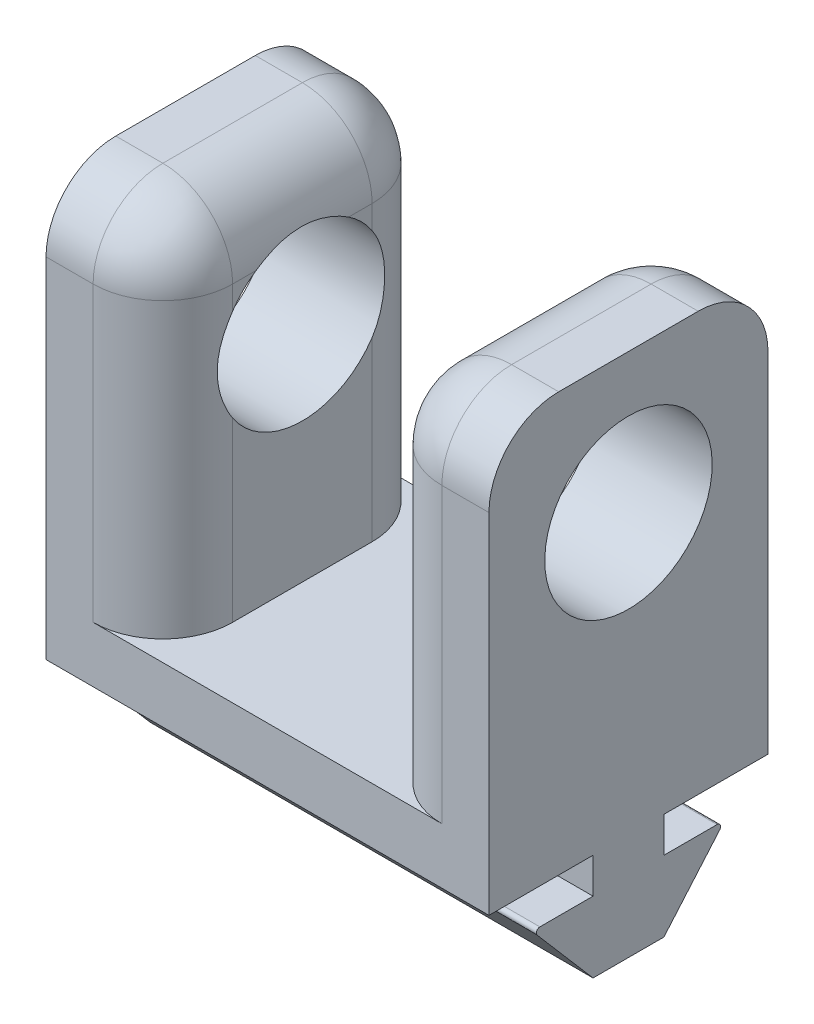
SolidWorks part; units mm, degrees
ref_plane "Front Plane" through (0, 0, 0) normal (0, 0, 1) x (1, 0, 0)
ref_plane "Top Plane" through (0, 0, 0) normal (0, 1, 0) x (1, 0, 0)
ref_plane "Right Plane" through (0, 0, 0) normal (1, 0, 0) x (0, 0, -1)
sketch "Sketch1" plane through (0, 0, 0) normal (0, 1, 0) x (1, 0, 0)
  line L1 (38.1, -25.4) -> (-38.1, -25.4)
  line L2 (38.1, -25.4) -> (38.1, 25.4)
  line L3 (38.1, 25.4) -> (-38.1, 25.4)
  line L4 (-38.1, -25.4) -> (-38.1, 25.4)
  line L5 (38.1, -25.4) -> (-38.1, 25.4) construction
  line L6 (38.1, 25.4) -> (-38.1, -25.4) construction
  point P0 (0, 0)
  dimension "D1" = 76.2
  dimension "D2" = 50.8
sketch "Sketch10" plane through (0, 0, 0) normal (1, 0, 0) x (0, 0, -1)
  line L0 (-12.7, 0) -> (0, 0) construction
  line L1 (0, 0) -> (0, -12.7) construction
  line L2 (0, 0) -> (0, 12.7) construction
  line L3 (0, 0) -> (12.7, 0) construction
  line L4 (6.35, 10.16) -> (-6.35, 10.16)
  line L5 (-6.5427, 9.7405) -> (-2.54, 5.08)
  line L6 (6.5427, 9.7405) -> (2.54, 5.08)
  line L7 (2.54, 5.08) -> (-2.54, 5.08)
  line L8 (-5.08, -2.54) -> (-5.08, 2.54)
  line L9 (-5.08, 2.54) -> (-9.7405, 6.5427)
  line L10 (-10.16, -6.35) -> (-10.16, 6.35)
  line L11 (-9.7405, -6.5427) -> (-5.08, -2.54)
  line L12 (-12.7, -2.54) -> (-12.7, 2.54)
  line L13 (-12.7, 2.54) -> (-10.16, 2.54)
  line L14 (-10.16, 2.54) -> (-10.16, -2.54)
  line L15 (-10.16, -2.54) -> (-12.7, -2.54)
  line L16 (2.54, 12.7) -> (-2.54, 12.7)
  line L17 (-2.54, 12.7) -> (-2.54, 10.16)
  line L18 (-2.54, 10.16) -> (2.54, 10.16)
  line L19 (2.54, 10.16) -> (2.54, 12.7)
  line L20 (2.54, -12.7) -> (-2.54, -12.7)
  line L21 (2.54, -5.08) -> (-2.54, -5.08)
  line L23 (6.35, -10.16) -> (-6.35, -10.16)
  line L24 (-2.54, -12.7) -> (-2.54, -10.16)
  line L26 (2.54, -12.7) -> (2.54, -10.16)
  line L27 (-2.54, -10.16) -> (2.54, -10.16)
  line L28 (-2.54, -5.08) -> (-6.5427, -9.7405)
  line L29 (2.54, -5.08) -> (6.5427, -9.7405)
  line L30 (5.08, -2.54) -> (5.08, 2.54)
  line L31 (12.7, -2.54) -> (12.7, 2.54)
  line L32 (12.7, 2.54) -> (10.16, 2.54)
  line L33 (10.16, 2.54) -> (10.16, -2.54)
  line L34 (10.16, -2.54) -> (12.7, -2.54)
  line L35 (10.16, -6.35) -> (10.16, 6.35)
  line L36 (5.08, 2.54) -> (9.7405, 6.5427)
  line L37 (5.08, -2.54) -> (9.7405, -6.5427)
  arc A0 (-10.16, -6.35) -> (-9.7405, -6.5427) centre (-9.906, -6.35) ccw
  arc A1 (-9.7405, 6.5427) -> (-10.16, 6.35) centre (-9.906, 6.35) ccw
  arc A2 (6.35, 10.16) -> (6.5427, 9.7405) centre (6.35, 9.906) cw
  arc A3 (-6.35, 10.16) -> (-6.5427, 9.7405) centre (-6.35, 9.906) ccw
  arc A4 (-6.35, -10.16) -> (-6.5427, -9.7405) centre (-6.35, -9.906) cw
  arc A6 (6.5427, -9.7405) -> (6.35, -10.16) centre (6.35, -9.906) cw
  arc A8 (9.7405, -6.5427) -> (10.16, -6.35) centre (9.906, -6.35) ccw
  arc A9 (10.16, 6.35) -> (9.7405, 6.5427) centre (9.906, 6.35) ccw
  point P4 (0, 5.08)
  point P10 (0, 10.16)
  point P17 (-5.08, 0)
  point P20 (-10.16, 0)
  point P30 (-12.7, 0)
  point P35 (0, 12.7)
  point P39 (0, -12.7)
  point P42 (0, -5.08)
  point P46 (0, -10.16)
  point P52 (5.08, 0)
  point P55 (12.7, 0)
  point P60 (10.16, 0)
  dimension "D1" = 0.254
  dimension "D16" = 0.254
  dimension "D2" = 5.08
  dimension "D3" = 5.08
  dimension "D4" = 2.54
  dimension "D5" = 2.54
  dimension "D6" = 5.08
  dimension "D7" = 12.7
  dimension "D8" = 5.08
  dimension "D9" = 12.7
  dimension "D10" = 5.08
  dimension "D11" = 5.08
  dimension "D12" = 12.7
  dimension "D13" = 5.08
  dimension "D14" = 5.08
  dimension "D15" = 2.54
extrude "Boss-Extrude3" add sketch "Sketch10" against normal blind 31.75 separate body contours L15 L10 L13 | L9 A1 L10 A0 L11 L8 | L4 A3 L5 L7 L6 A2 | L4 L19 L17 | A6 L29 L21 L28 A4 L23 | L20 L26 L23 L24 | L35 A9 L36 L30 L37 A8 L33 | L33 L34 L31 L32 region at (0, 8.0055, 0) region at (0, 11.43, 0) region at (0, 0, 8.0055) region at (0, 0, 11.43) region at (0, -11.43, 0) region at (0, -8.0055, 0) region at (0, 0, -8.0055) region at (0, 0, -11.43)
sketch "Sketch11" plane through (0, 0, 0) normal (1, 0, 0) x (0, 0, -1)
  line L0 (10, 12.7) -> (-10, 12.7)
  line L2 (-10, 12.7) -> (-10, 16.7)
  line L3 (-10, 16.7) -> (10, 16.7)
  line L4 (10, 16.7) -> (10, 12.7)
  line L5 (2.54, 12.7) -> (-2.54, 12.7) construction
  point P3 (0, 12.7)
  dimension "D1" = 4
  dimension "D2" = 20
extrude "Boss-Extrude4" add sketch "Sketch11" along direction (1, 0, 0) on the side against the normal up to surface (31.75 mm away) up to face at (-31.75, 9.5805, 0)
sketch "Sketch12" plane through (-31.75, 0, 0) normal (-1, 0, 0) x (0, 0, 1)
  line L0 (0, 0) -> (-15.4836, 16.021)
  line L1 (-15.4836, 16.021) -> (-15.4836, -14.9642)
  line L2 (-15.4836, -14.9642) -> (16.0161, -14.9642)
  line L3 (16.0161, -14.9642) -> (16.0161, 15.4789)
  line L4 (16.0161, 15.4789) -> (0, 0)
extrude "Cut-Extrude1" cut sketch "Sketch12" against normal through all
sketch "Sketch13" plane through (0, 0, -10) normal (0, 0, -1) x (-1, 0, 0)
  line L0 (15.875, 16.7) -> (15.875, 42.7) construction
  line L1 (31.75, 16.7) -> (0, 16.7) construction
  line L2 (23.375, 42.7) -> (8.375, 42.7) construction
  line L3 (8.375, 42.7) -> (8.375, 16.7)
  line L4 (8.375, 16.7) -> (23.375, 16.7) construction
  line L5 (23.375, 16.7) -> (23.375, 42.7)
  line L6 (0, 16.7) -> (0, 42.7)
  line L7 (0, 42.7) -> (8.375, 42.7)
  line L8 (23.375, 42.7) -> (31.75, 42.7)
  line L9 (31.75, 42.7) -> (31.75, 16.7)
  line L10 (0, 16.7) -> (8.375, 16.7)
  line L11 (23.375, 16.7) -> (31.75, 16.7)
  point P7 (15.875, 42.7)
  dimension "D1" = 26
  dimension "D2" = 15
extrude "Boss-Extrude5" add sketch "Sketch13" against normal through all
sketch "Sketch16" plane through (-23.375, 0, 0) normal (1, 0, 0) x (0, 0, -1)
  line L0 (0, 32.7) -> (0, 16.7) construction
  line L1 (10, 16.7) -> (-10, 16.7) construction
  circle A0 centre (0, 32.7) radius 6
  dimension "D1" = 12
  dimension "D2" = 16
extrude "Cut-Extrude2" cut sketch "Sketch16" against normal through all both and the other way through all
fillet "Fillet1" radius 5 10 edges at (-27.5625, 42.7, 10) (-27.5625, 42.7, -10) (-4.1875, 42.7, -10) (-4.1875, 42.7, 10) (-23.375, 29.7, 10) (-23.375, 42.7, 0) (-23.375, 29.7, -10) (-8.375, 29.7, 10) (-8.375, 29.7, -10) (-8.375, 42.7, 0)
